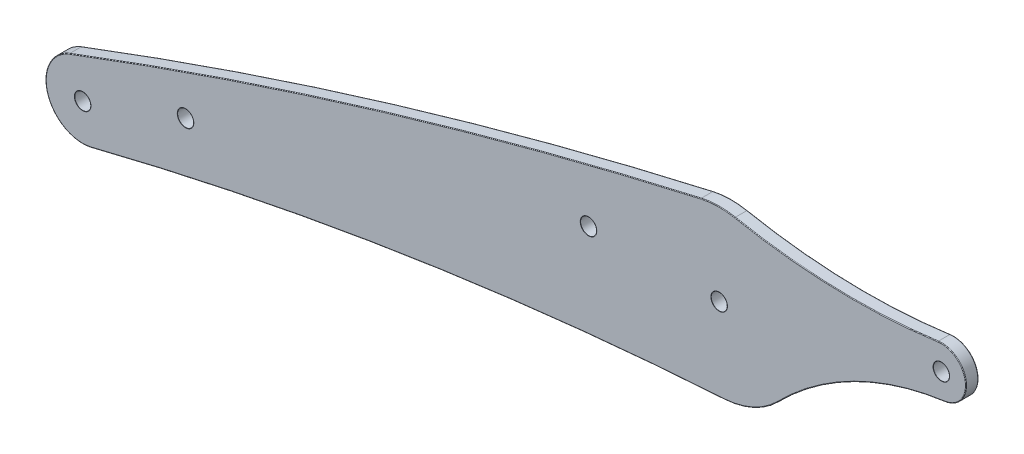
SolidWorks part; units mm, degrees
ref_plane "Front Plane" through (0, 0, 0) normal (0, 0, 1) x (1, 0, 0)
ref_plane "Top Plane" through (0, 0, 0) normal (0, 1, 0) x (1, 0, 0)
ref_plane "Right Plane" through (0, 0, 0) normal (1, 0, 0) x (0, 0, -1)
sketch "Sketch1" plane through (0, 0, 0) normal (0, 0, 1) x (1, 0, 0)
  line L0 (-220.8241, 163.1179) -> (-12.1462, 210.5473) construction
  line L1 (-220.8241, 163.1179) -> (-12.1462, 210.5473) construction
  circle A0 centre (-220.8241, 163.1179) radius 9 construction
  circle A1 centre (-66.1462, 198.2739) radius 10 construction
  circle A2 centre (-66.1462, 198.2739) radius 20 construction
  circle A3 centre (-12.1462, 210.5473) radius 6 construction
  arc A4 (-224.0153, 171.5332) -> (-70.5691, 217.7788) centre (183.7449, -903.7489) cw
  arc A5 (-218.6321, 154.3889) -> (-64.8925, 178.3133) centre (-11.6104, -670.0151) cw
  arc A6 (-62.2946, 217.8995) -> (-12.964, 216.4913) centre (-33.4074, 365.0917) ccw
  arc A7 (-51.8707, 184.2665) -> (-11.3378, 204.602) centre (-1.9063, 135.2403) cw
  arc A8 (-224.0153, 171.5332) -> (-218.6321, 154.3889) centre (-220.8241, 163.1179) ccw
  arc A9 (-62.2946, 217.8995) -> (-70.5691, 217.7788) centre (-66.1462, 198.2739) ccw
  arc A10 (-51.8707, 184.2665) -> (-64.8925, 178.3133) centre (-66.1462, 198.2739) cw
  arc A11 (-12.964, 216.4913) -> (-11.3378, 204.602) centre (-12.1462, 210.5473) cw
  arc A12 (-220.8241, 163.1179) -> (-12.1462, 210.5473) centre (56.9913, -576.4215) cw construction
  point P2 (-66.1462, 198.2739)
  point P26 (-195.8241, 172.0331)
  point P27 (-97.8962, 198.246)
  dimension "D1" = 18
  dimension "D2" = 20
  dimension "D3" = 40
  dimension "D4" = 12
  dimension "D5" = 850
  dimension "D6" = 1150
  dimension "D7" = 70
  dimension "D8" = 150
  dimension "D9" = 790
  dimension "D10" = 31.75
  dimension "D11" = 25
extrude "Boss-Extrude1" add sketch "Sketch1" against normal blind 3
sketch "Sketch6" plane through (0, 0, 0) normal (0, 0, 1) x (1, 0, 0)
  point P0 (-220.8241, 163.1179)
  point P3 (-195.8241, 172.0331)
  point P6 (-97.8962, 198.246)
  point P9 (-66.1462, 198.2739)
  point P12 (-12.1462, 210.5473)
hole_wizard "M3.5 Clearance Hole1" positions "Sketch6" profile "Sketch5" hole size "M3.5" standard "ISO"
sketch "Sketch5" plane through (-220.8241, 163.1179, 0) normal (1, 0, 0) x (0, -1, 0)
  line L0 (0, 0) -> (0, 11.1717)
  line L1 (0, 11.1717) -> (1.95, 10)
  line L2 (1.95, 10) -> (1.95, 0.025)
  line L3 (1.95, 0.025) -> (1.975, 0)
  line L5 (1.975, 0) -> (0, 0)
  line L6 (-1.95, 0.025) -> (-1.975, 0) construction
  line L10 (0, 11.1717) -> (-1.95, 10) construction
  line L11 (0, -6.35) -> (0, 107.95) construction
  dimension "Hole Dia." = 3.9
  dimension "Hole Depth" = 10
  dimension "Near C'Sink Dia." = 3.95
  dimension "Near C'Sink Angle" = 90
  dimension "Drill Angle" = 118
fillet "Fillet1" radius 0.15 26 edges at (-142.3109, 169.8762, -3) (-57.8306, 180.0846, -3) (-33.2966, 197.8075, -3) (-6.2016, 211.3604, -3) (-37.6876, 215.1528, -3) (-66.4382, 218.2718, -3) (-148.0988, 197.3322, -3) (-229.4108, 160.4218, -3) (-10.1962, 210.5473, -3) (-64.1962, 198.2739, -3) (-95.9462, 198.246, -3) (-193.8741, 172.0331, -3) (-218.8741, 163.1179, -3) (-148.0988, 197.3322, 0) (-66.4382, 218.2718, 0) (-37.6876, 215.1528, 0) (-6.2016, 211.3604, 0) (-33.2966, 197.8075, 0) (-57.8306, 180.0846, 0) (-142.3109, 169.8762, 0) (-229.4108, 160.4218, 0) (-10.1712, 210.5473, 0) (-64.1712, 198.2739, 0) (-95.9212, 198.246, 0) (-193.8491, 172.0331, 0) (-218.8491, 163.1179, 0)
